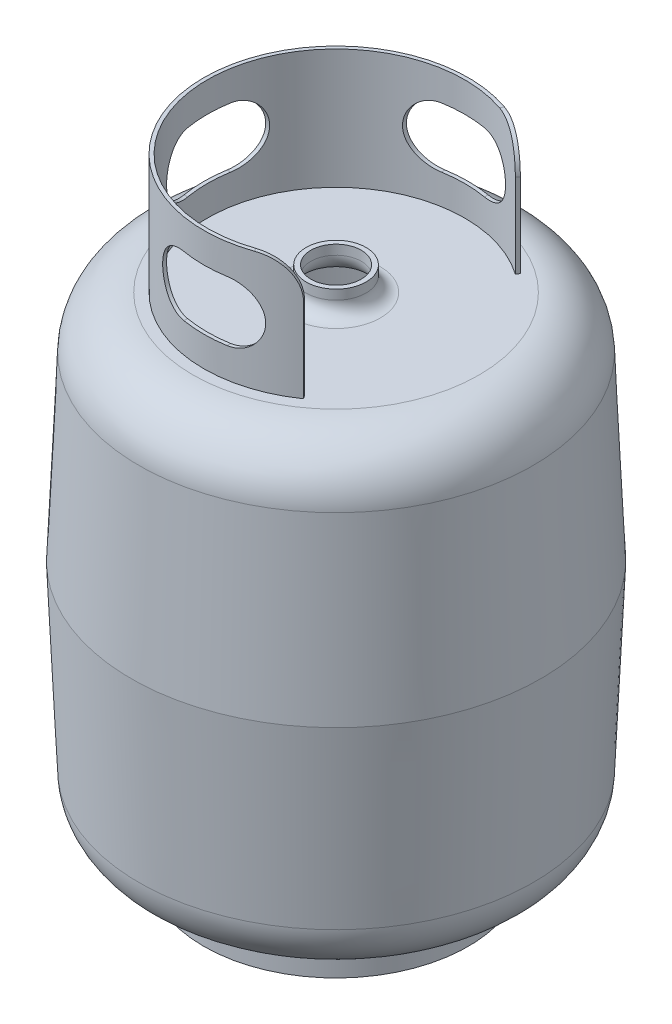
SolidWorks part; units mm, degrees
material "1060 Alloy"
ref_plane "Front Plane" through (0, 0, 0) normal (0, 0, 1) x (1, 0, 0)
ref_plane "Top Plane" through (0, 0, 0) normal (0, 1, 0) x (1, 0, 0)
ref_plane "Right Plane" through (0, 0, 0) normal (1, 0, 0) x (0, 0, -1)
sketch "Sketch1" plane through (0, 0, 0) normal (0, 0, 1) x (1, 0, 0)
  line L0 (0, 193.75) -> (0, -193.75) construction
  line L1 (0, 0) -> (-170.9593, 0) construction
  line L2 (0, -193.75) -> (-119.4219, -193.75)
  line L3 (-164.379, -150.7129) -> (-170.9593, 0)
  line L4 (-170.9593, 0) -> (-164.379, 150.7129)
  line L5 (-119.4219, 193.75) -> (-37, 193.75)
  line L6 (-25, 205.75) -> (-25, 213.75)
  line L7 (-25, 213.75) -> (0, 213.75)
  line L8 (0, 213.75) -> (0, 193.75)
  line L9 (0, -193.75) -> (0, 193.75)
  arc A0 (-119.4219, -193.75) -> (-164.379, -150.7129) centre (-119.4219, -148.75) cw
  arc A1 (-164.379, 150.7129) -> (-119.4219, 193.75) centre (-119.4219, 148.75) cw
  arc A2 (-37, 193.75) -> (-25, 205.75) centre (-37, 205.75) ccw
  point P4 (0, 0)
  point P14 (-162.5, -193.75)
  point P19 (-25, 193.75)
  dimension "D7" = 45
  dimension "D8" = 45
  dimension "D9" = 12
  dimension "D1" = 387.5
  dimension "D2" = 325
  dimension "D3" = 92.5
  dimension "D4" = 92.5
  dimension "D5" = 20
  dimension "D6" = 25
revolve "Revolve1" add sketch "Sketch1" angle 360 about L9
shell "Shell2" thickness 4 removed face at (0, 213.75, -25)
sketch "Sketch6" plane through (0, 193.75, 0) normal (0, 1, 0) x (1, 0, 0)
  line L0 (0, 191.5146) -> (0, -191.5146) construction
  line L1 (-194.9143, 0) -> (194.9143, 0) construction
  line L2 (61.6147, 87.9948) -> (63.3354, 90.4523)
  line L3 (61.6147, -87.9948) -> (63.3354, -90.4523)
  arc A1 (63.3354, 90.4523) -> (63.3354, -90.4523) centre (0, 0) ccw
  arc A2 (61.6147, 87.9948) -> (61.6147, -87.9948) centre (0, 0) ccw
  circle A3 centre (0, 0) radius 119.4219 construction
  point P9 (0, 0)
  point P12 (0, 0)
  dimension "D1" = 3
  dimension "D2" = 12
  dimension "D3" = 55
  dimension "D4" = 55
extrude "Boss-Extrude3" add sketch "Sketch6" along normal blind 100
fillet "Fillet2" radius 30 1 edges at (62.475, 293.75, 89.2236)
fillet "Fillet3" radius 30 1 edges at (62.475, 293.75, -89.2236)
sketch "Sketch7" plane through (0, 0, 0) normal (0, 0, 1) x (1, 0, 0)
  line L0 (-18, 243.75) -> (18, 243.75) construction
  line L1 (-18, 268.75) -> (18, 268.75)
  line L2 (-18, 218.75) -> (18, 218.75)
  line L3 (36.3785, 293.75) -> (-110.4219, 293.75) construction
  arc A0 (-18, 268.75) -> (-18, 218.75) centre (-18, 243.75) ccw
  arc A1 (18, 218.75) -> (18, 268.75) centre (18, 243.75) ccw
  point P2 (0, 243.75)
  dimension "D1" = 18
  dimension "D2" = 50
  dimension "D3" = 50
  dimension "D4" = 36
extrude "Cut-Extrude2" cut sketch "Sketch7" against normal through all both and the other way through all
pattern_circular "CirPattern2" count 2 every 90 about axis through (0, 293.75, 0) along (0, -1, 0) of "Cut-Extrude2"
sketch "Sketch8" plane through (0, -193.75, 0) normal (0, -1, 0) x (1, 0, 0)
  circle A0 centre (0, 0) radius 110.4219
  circle A1 centre (0, 0) radius 107.4219
  circle A2 centre (0, 0) radius 119.4219 construction
  dimension "D1" = 3
  dimension "D2" = 12
extrude "Boss-Extrude4" add sketch "Sketch8" along normal blind 30
equation "\"A\"= 387.50"
equation "\"B\"= 325"
equation "\"D1@Sketch1\"=\"A\""
equation "\"D2@Sketch1\"=\"B\""
